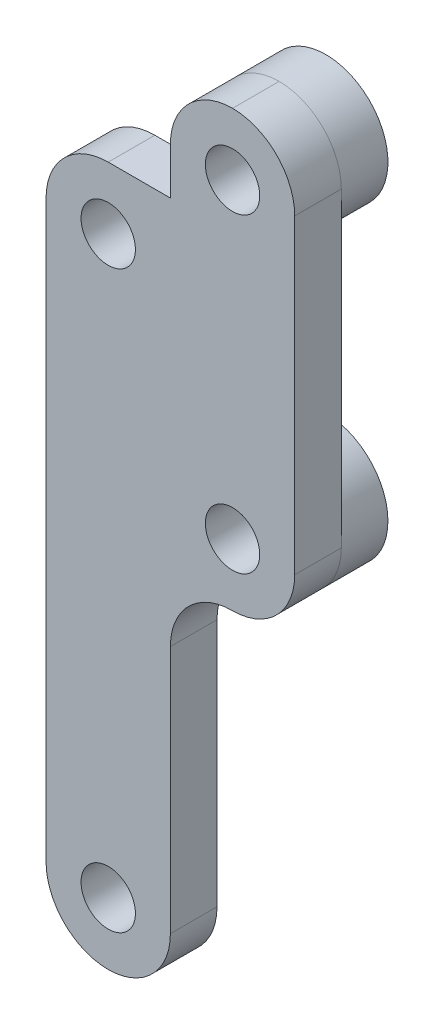
SolidWorks part; units mm, degrees
ref_plane "Plano frontal" through (0, 0, 0) normal (0, 0, 1) x (1, 0, 0)
ref_plane "Plano superior" through (0, 0, 0) normal (0, 1, 0) x (1, 0, 0)
ref_plane "Plano direito" through (0, 0, 0) normal (1, 0, 0) x (0, 0, -1)
sketch "Esboço1" plane through (0, 0, 0) normal (0, 0, 1) x (1, 0, 0)
  line L0 (4, -4) -> (-4, -4)
  line L1 (-4, 24) -> (4, 24)
  line L2 (-4, 24) -> (-4, 17)
  line L3 (-4, -28) -> (-4, -4)
  line L4 (4, 24) -> (4, -4)
  line L5 (-4, -28) -> (-12, -28)
  line L7 (-12, -28) -> (-12, 17)
  line L8 (-12, 17) -> (-4, 17)
  circle A0 centre (-8, 13) radius 1.75
  circle A1 centre (0, 0) radius 1.75
  circle A2 centre (0, 20) radius 1.75
  circle A3 centre (-8, -24) radius 1.75
  point P5 (0, 0)
  point P11 (-12, -5.5)
  point P20 (0, 24)
  point P23 (-8, -28)
  dimension "D1" = 3.5
  dimension "D4" = 8
  dimension "D6" = 4
  dimension "D5" = 20
  dimension "D3" = 37
  dimension "D2" = 4
  dimension "D7" = 4
  dimension "D8" = 7
extrude "Ressalto-extrusão1" add sketch "Esboço1" along normal blind 3
sketch "Esboço2" plane through (0, 0, 0) normal (0, 0, -1) x (-1, 0, 0)
  circle A0 centre (0, 20) radius 4
  circle A1 centre (0, 0) radius 4
  circle A2 centre (0, 20) radius 1.75
  circle A3 centre (0, 0) radius 1.75
  circle A6 centre (0, 20) radius 1.75 construction
  dimension "D1" = 8
extrude "Ressalto-extrusão2" add sketch "Esboço2" along normal blind 3
fillet "Filete1" radius 4 7 edges at (4, 24, 1.5) (-4, 24, 1.5) (-12, 17, 1.5) (-12, -28, 1.5) (-4, -28, 1.5) (-4, -4, 1.5) (4, -4, 1.5) tangent propagation no
equation "\"D2@Esboço1\"=\"D6@Esboço1\""
equation "\"D7@Esboço1\"=\"D2@Esboço1\""
